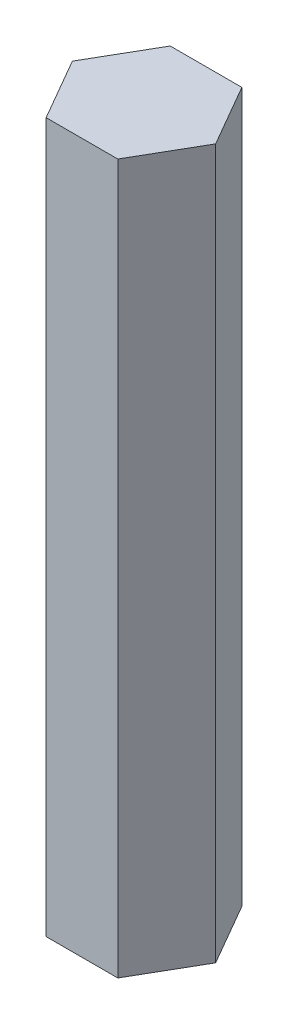
SolidWorks part; units mm, degrees
ref_plane "Front Plane" through (0, 0, 0) normal (0, 0, 1) x (1, 0, 0)
ref_plane "Top Plane" through (0, 0, 0) normal (0, 1, 0) x (1, 0, 0)
ref_plane "Right Plane" through (0, 0, 0) normal (1, 0, 0) x (0, 0, -1)
sketch "Esquisse3" plane through (0, 0, 0) normal (0, 1, 0) x (1, 0, 0)
  line L1 (3, 0) -> (1.5, 2.5981)
  line L2 (1.5, 2.5981) -> (-1.5, 2.5981)
  line L3 (-1.5, 2.5981) -> (-3, 0)
  line L4 (-3, 0) -> (-1.5, -2.5981)
  line L5 (-1.5, -2.5981) -> (1.5, -2.5981)
  line L6 (1.5, -2.5981) -> (3, 0)
  circle A0 centre (0, 0) radius 2.5981 construction
  dimension "D1" = 3
  dimension "D2" = 1.5
extrude "Boss.-Extru.1" add sketch "Esquisse3" along normal blind 29.7 contours L2 L3 L4 L5 L6 L1
ref_plane "Plan1" through (0, 0, 0) normal (0, 0, 1) x (1, 0, 0)
ref_point "Point1"
ref_axis "Axe1" through (0, 0, 0) along (0, 1, 0)
